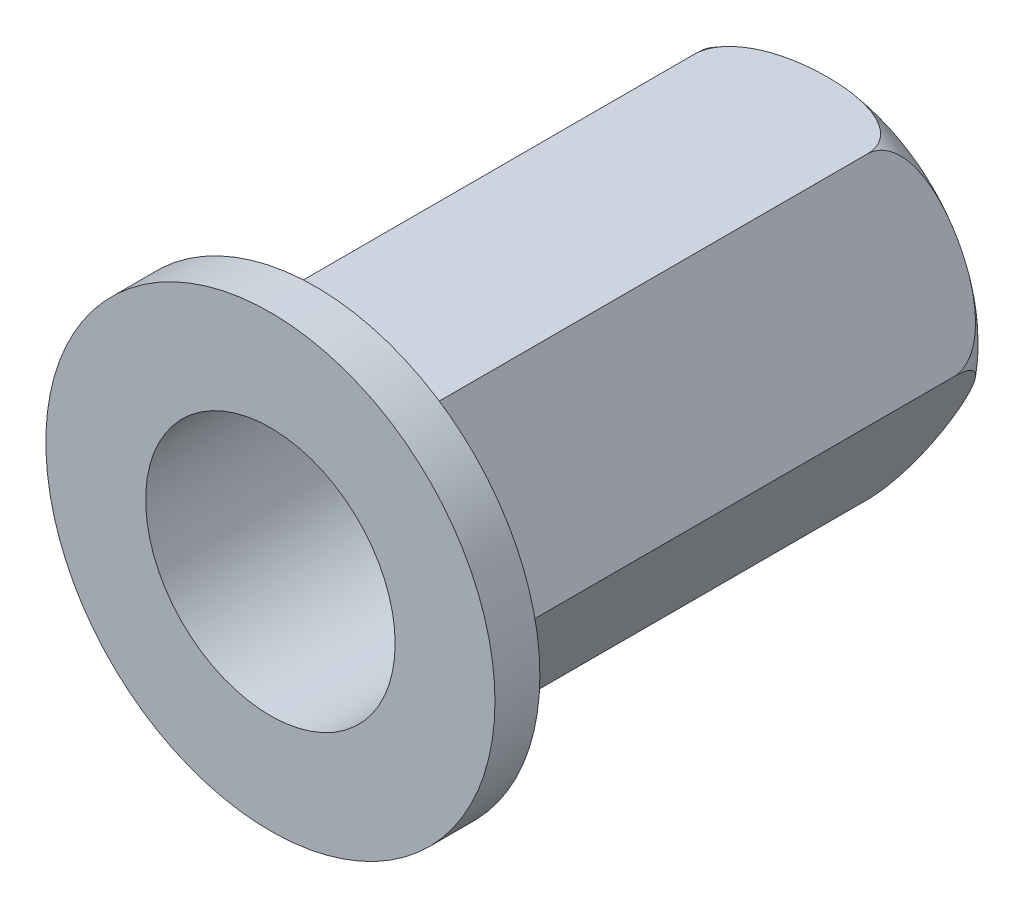
SolidWorks part; units mm, degrees
ref_plane "Front" through (0, 0, 0) normal (0, 0, 1) x (1, 0, 0)
ref_plane "Top" through (0, 0, 0) normal (0, 1, 0) x (1, 0, 0)
ref_plane "Right" through (0, 0, 0) normal (1, 0, 0) x (0, 0, -1)
sketch "Sketch3" plane through (0, 0, 0) normal (0, 0, 1) x (1, 0, 0)
  circle A0 centre (0, 0) radius 9
extrude "BaseHead" add sketch "Sketch3" against normal blind 1.8
sketch "Sketch4" plane through (2.8191, -1.6346, -1.8) normal (0, 0, -1) x (-1, 0, 0)
  line L1 (-0.645, 7.6346) -> (-4.1091, 1.6346)
  line L2 (-4.1091, 1.6346) -> (-0.645, -4.3654)
  line L3 (-0.645, -4.3654) -> (6.2832, -4.3654)
  line L4 (6.2832, -4.3654) -> (9.7473, 1.6346)
  line L5 (9.7473, 1.6346) -> (6.2832, 7.6346)
  line L6 (6.2832, 7.6346) -> (-0.645, 7.6346)
  circle A0 centre (2.8191, 1.6346) radius 6 construction
  circle A1 centre (2.8191, 1.6346) radius 6 construction
  circle A2 centre (2.8191, 1.6346) radius 9 construction
  dimension "s" = 12
extrude "BaseBody" add sketch "Sketch4" along normal blind 21
sketch "Sketch5" plane through (4.0795, 0.9752, 0) normal (0, 0, 1) x (1, 0, 0)
  circle A0 centre (-4.0795, -0.9752) radius 5
  circle A1 centre (-4.0795, -0.9752) radius 9 construction
extrude "Hole1" cut sketch "Sketch5" against normal blind 7.3
sketch "Sketch6" plane through (1.8124, 4.1988, -7.3) normal (0, 0, 1) x (1, 0, 0)
  circle A0 centre (-1.8124, -4.1988) radius 3.5
  circle A1 centre (-1.8124, -4.1988) radius 5 construction
  dimension "D1" = 7
extrude "Hole2" cut sketch "Sketch6" against normal through all
cosmetic thread "ThreadCosmetic1" [suppressed] parameters "D2"=8
sketch "Sketch7" plane through (8.6603, 0, 20.3033) normal (0, 1, 0) x (-1, 0, 0)
  line L0 (8.6603, 2.4967) -> (8.6603, -3.5015) construction
  line L3 (15.5885, -43.1033) -> (12.1244, -43.1033) construction
  line L5 (15.5885, -43.1033) -> (15.5885, -22.1033) construction
  line L6 (15.5885, -43.1033) -> (13.2551, -43.1033)
  line L8 (15.5885, -43.1033) -> (15.5885, -40.77)
  arc A0 (13.2551, -43.1033) -> (15.5885, -40.77) centre (13.2551, -40.77) ccw
revolve "Cut-Revolve1" cut sketch "Sketch7" angle 360 about L0
fillet "Fillet1" radius 0.9 6 edges at (0, -6, -1.8) (-5.1962, -3, -1.8) (-5.1962, 3, -1.8) (0, 6, -1.8) (5.1962, 3, -1.8) (5.1962, -3, -1.8)
chamfer "Chamfer1" distance 0.4667 angle 45 1 edges at (3.5, 0, -22.8)
chamfer "Chamfer2" distance 1.5 angle 45 1 edges at (3.5, 0, -7.3)
sketch "Sketch9" plane through (0, 0, 0) normal (1, 0, 0) x (0, 0, -1)
  line L0 (-5.9053, 0) -> (27.963, 0) construction
  line L1 (22.0833, -3.5) -> (22.0833, -3)
  line L2 (22.0833, -3) -> (22.5833, -3)
  line L3 (22.5833, -3) -> (22.5833, -3.5)
  line L4 (22.5833, -3.5) -> (22.3333, -3.933)
  line L5 (22.3333, -3.933) -> (22.0833, -3.5)
  line L6 (22.3333, -3.5) -> (22.3333, 3.5) construction
  dimension "D1" = 0.5
  dimension "D2" = 7
revolve "Cut-Revolve10" [suppressed] cut sketch "Sketch9" angle 360 about L0
pattern_linear "LPattern10" [suppressed] count 25 spacing 0.6 along (0, 0, 1) of bodies 109
equation "\"D1@Chamfer1\" = \"D1@Sketch6\" / 15"
equation "\"D1@Chamfer2\" =  ( \"d1@Sketch5\" - \"D1@Sketch6\" )  / 2"
equation "\"r@Sketch7\" = \"D1@Chamfer1\" * 5"
equation "\"D1@Sketch9\" = (  \"D2@ThreadCosmetic1\" - \"D1@Sketch6\" )  / 2"
equation "\"D3@LPattern10\" = \"D1@Sketch9\" * 1.2 "
equation "\"D1@LPattern10\" =  (  \"l@BaseBody\" + \"k@BaseHead\" - \"l1@Hole1\" )  / \"D3@LPattern10\" - 1"
equation "\"D1@Fillet1\" = \"dk@Sketch3\" / 20"
equation "\"D2@Sketch9\" = \"D1@Sketch6\""
